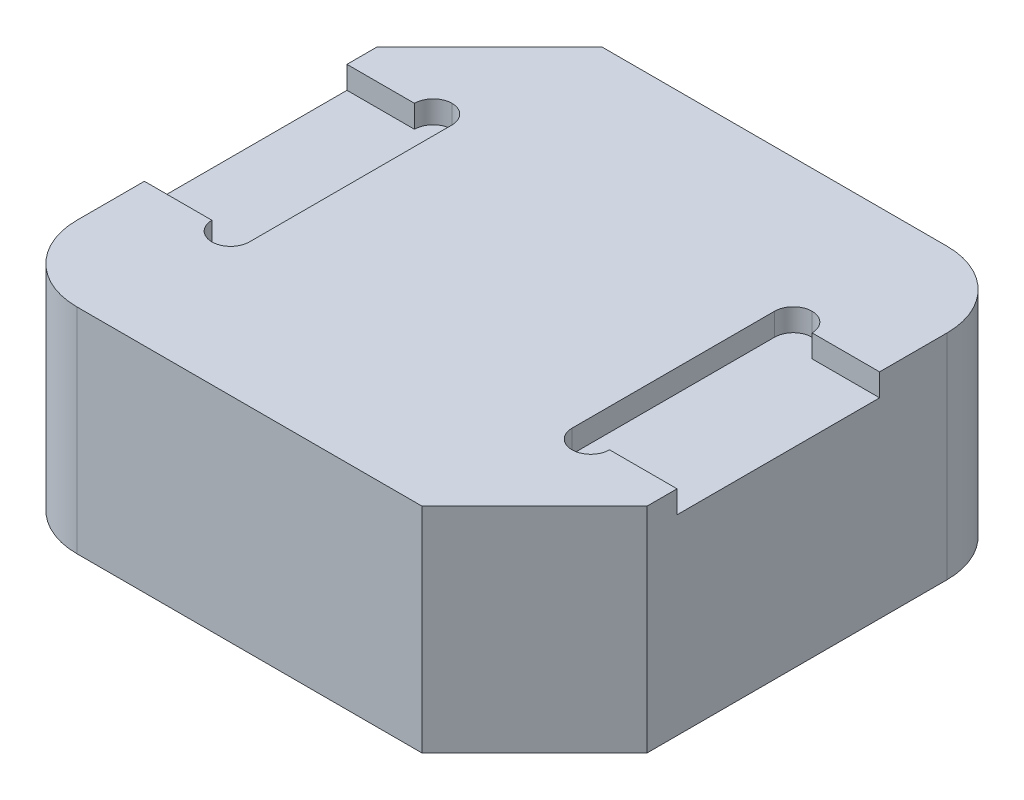
SolidWorks part; units mm, degrees
ref_plane "Front Plane" through (0, 0, 0) normal (0, 0, 1) x (1, 0, 0)
ref_plane "Top Plane" through (0, 0, 0) normal (0, 1, 0) x (1, 0, 0)
ref_plane "Right Plane" through (0, 0, 0) normal (1, 0, 0) x (0, 0, -1)
sketch "Sketch1" plane through (0, 0, 0) normal (0, 1, 0) x (1, 0, 0)
  line L1 (-3.55, -3.25) -> (3.55, -3.25)
  line L2 (-3.55, -3.25) -> (-3.55, 3.25)
  line L3 (-3.55, 3.25) -> (3.55, 3.25)
  line L4 (3.55, -3.25) -> (3.55, 3.25)
  line L5 (-3.55, -3.25) -> (3.55, 3.25) construction
  line L6 (-3.55, 3.25) -> (3.55, -3.25) construction
  point P0 (0, 0)
  dimension "D1" = 7.1
  dimension "D2" = 6.5
extrude "Boss-Extrude1" add sketch "Sketch1" along normal blind 2.85
chamfer "Chamfer1" distance 1.5 angle 45 2 edges at (3.55, 1.425, 3.25) (-3.55, 1.425, -3.25)
fillet "Fillet1" radius 1 2 edges at (3.55, 1.425, -3.25) (-3.55, 1.425, 3.25)
sketch "Sketch2" plane through (0, 2.85, 0) normal (0, 1, 0) x (1, 0, 0)
  line L0 (-1.5675, 0) -> (1.5675, 0) construction
  line L1 (3.55, 1.35) -> (2.65, 1.35)
  line L2 (3.55, 1.35) -> (3.55, -1.35)
  line L3 (3.55, -1.35) -> (2.65, -1.35)
  line L4 (2.65, 1.35) -> (2.65, -1.35)
  line L5 (3.55, -1.75) -> (3.55, 2.25) construction
  point P4 (3.55, 0)
  dimension "D1" = 2.7
  dimension "D2" = 0.9
extrude "Cut-Extrude1" cut sketch "Sketch2" against normal blind 0.3
sketch "Sketch3" plane through (0, 2.85, 0) normal (0, 1, 0) x (1, 0, 0)
  line L0 (-1.5675, 0) -> (1.5675, 0) construction
  line L1 (2.65, 1.6) -> (2.15, 1.6)
  line L2 (2.65, 1.6) -> (2.65, -1.6)
  line L3 (2.65, -1.6) -> (2.15, -1.6)
  line L4 (2.15, 1.6) -> (2.15, -1.6)
  line L5 (2.65, 1.35) -> (2.65, -1.35) construction
  point P4 (2.65, 0)
  dimension "D1" = 3.2
  dimension "D2" = 0.5
extrude "Cut-Extrude2" cut sketch "Sketch3" against normal blind 0.3
fillet "Fillet2" radius 0.25 4 edges at (2.65, 2.7, 1.6) (2.15, 2.7, 1.6) (2.65, 2.7, -1.6) (2.15, 2.7, -1.6)
mirror "Mirror1" about plane through (0, 0, 0) normal (1, 0, 0) of "Fillet2", "Cut-Extrude2", "Cut-Extrude1"
